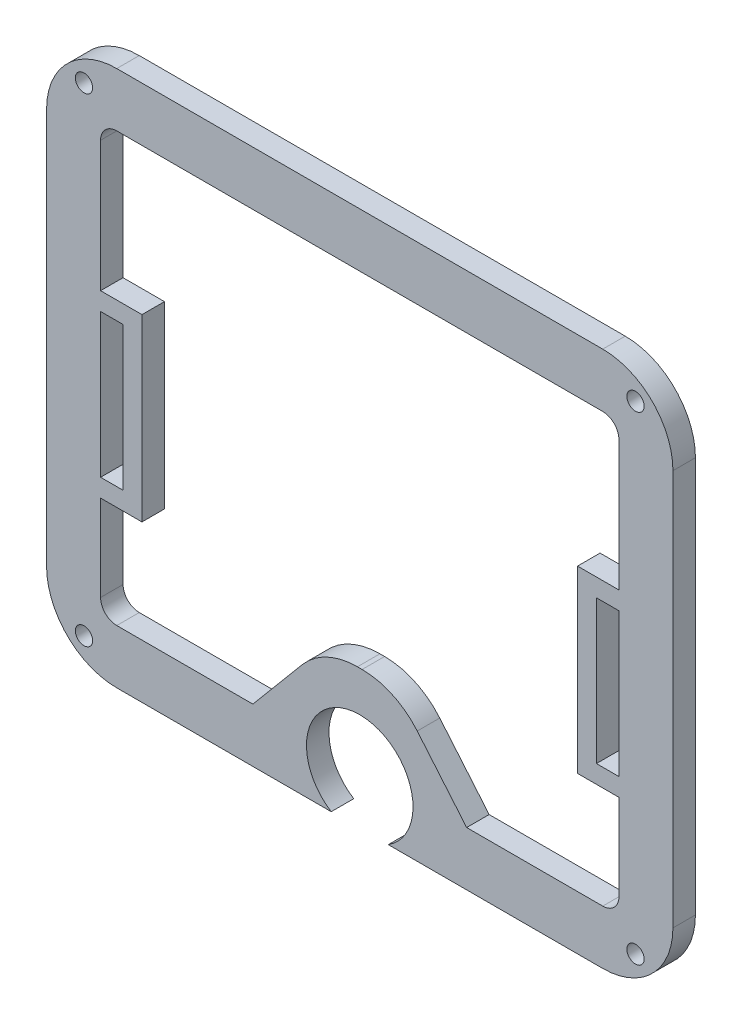
SolidWorks part; units mm, degrees
material "Delrin"
ref_plane "Front Plane" through (0, 0, 0) normal (0, 0, 1) x (1, 0, 0)
ref_plane "Top Plane" through (0, 0, 0) normal (0, 1, 0) x (1, 0, 0)
ref_plane "Right Plane" through (0, 0, 0) normal (1, 0, 0) x (0, 0, -1)
sketch "Sketch1" plane through (0, 0, 0) normal (0, 0, 1) x (1, 0, 0)
  line L0 (-17.145, -18.923) -> (-2.0127, -18.923)
  line L1 (-18.288, 13.97) -> (-18.288, -13.97)
  line L2 (-17.145, -15.113) -> (-7.5425, -15.113)
  line L3 (7.5425, -15.113) -> (17.145, -15.113)
  line L4 (18.288, 13.97) -> (18.288, -13.97)
  line L5 (-1000, 0) -> (49000, 0) construction
  line L7 (2.0127, -18.923) -> (17.145, -18.923)
  line L8 (17.145, 15.113) -> (-17.145, 15.113)
  line L9 (-7.5425, -15.113) -> (-4.0566, -10.9586)
  line L10 (-22.098, 13.97) -> (-22.098, -13.97)
  line L11 (7.5425, -15.113) -> (4.0566, -10.9586)
  line L12 (-0.1651, -9.144) -> (0.1651, -9.144)
  line L13 (22.098, 13.97) -> (22.098, -13.97)
  line L14 (17.145, 18.923) -> (-17.145, 18.923)
  line L18 (0, 12.5532) -> (0, -24.2768) construction
  arc A0 (2.0127, -18.923) -> (-2.0127, -18.923) centre (0, -15.748) ccw
  arc A1 (-17.145, -15.113) -> (-18.288, -13.97) centre (-17.145, -13.97) cw
  arc A2 (-0.1651, -9.144) -> (-4.0566, -10.9586) centre (-0.1651, -14.224) ccw
  arc A3 (18.288, -13.97) -> (17.145, -15.113) centre (17.145, -13.97) cw
  arc A4 (17.145, 15.113) -> (18.288, 13.97) centre (17.145, 13.97) cw
  arc A5 (-17.145, -18.923) -> (-22.098, -13.97) centre (-17.145, -13.97) cw
  arc A6 (22.098, -13.97) -> (17.145, -18.923) centre (17.145, -13.97) cw
  arc A7 (17.145, 18.923) -> (22.098, 13.97) centre (17.145, 13.97) cw
  arc A8 (-17.145, 18.923) -> (-22.098, 13.97) centre (-17.145, 13.97) ccw
  circle A9 centre (-19.4575, 16.891) radius 0.6096
  circle A10 centre (19.4575, 16.891) radius 0.6096
  arc A11 (-17.145, 15.113) -> (-18.288, 13.97) centre (-17.145, 13.97) ccw
  arc A12 (0.1651, -9.144) -> (4.0566, -10.9586) centre (0.1651, -14.224) cw
  circle A13 centre (19.4575, -16.891) radius 0.6096
  circle A14 centre (-19.4575, -16.891) radius 0.6096
  arc A18 (7.5425, -15.113) -> (-7.5425, -15.113) centre (0, -15.748) ccw construction
  point P0 (0, 0)
  dimension "D4" = 3.175
  dimension "D6" = 37.846
  dimension "D7" = 44.196
  dimension "D8" = 3.81
  dimension "D9" = 6.604
  dimension "D5" = 1.2192
  dimension "D2" = 4.953
  dimension "D3" = 7.5184
  dimension "D10" = 5.08
  dimension "D11" = 5.08
  dimension "D12" = 16.891
  dimension "D13" = 19.4575
extrude "Boss-Extrude1" add sketch "Sketch1" along normal blind 1.5875
sketch "Sketch2" plane through (-18.288, 0, 0) normal (1, 0, 0) x (0, 0, -1)
  line L0 (0, 3.5062) -> (-1.5875, 3.5062)
  line L1 (0, -6.625) -> (-1.5875, -6.625) construction
  line L2 (-1.5875, -15.113) -> (0, -15.113)
  line L3 (-1.5875, -15.113) -> (0, -15.113) construction
  line L4 (0, -13.97) -> (0, 13.97)
  line L5 (0, 13.97) -> (-1.5875, 13.97)
  line L6 (-1.5875, 13.97) -> (-1.5875, -13.97)
  line L7 (0, 13.97) -> (-1.5875, 13.97)
  line L8 (0, -13.97) -> (0, 4.7762)
  line L9 (-1.5875, -15.113) -> (-1.5875, -7.895)
  line L10 (-1.5875, 4.7762) -> (-1.5875, -13.97)
  line L11 (-1.5875, -13.97) -> (0, -13.97)
  line L12 (0, -15.113) -> (0, -7.895)
  line L13 (0, 4.7762) -> (-1.5875, 4.7762)
  line L14 (-1.5875, 3.5062) -> (-1.5875, -6.6447)
  line L15 (-1.5875, 4.7762) -> (-1.5875, 3.5062)
  line L16 (0, 3.5062) -> (0, 4.7762)
  line L17 (0, -7.9147) -> (0, 1.6011)
  line L18 (-1.5875, -7.9147) -> (-1.5875, -6.6447)
  line L19 (0, -6.625) -> (-1.5875, -6.625)
  line L21 (0, -7.895) -> (-1.5875, -7.895)
  line L22 (0, -7.895) -> (0, -13.97)
  line L23 (-1.5875, -7.895) -> (-1.5875, -13.97)
  line L24 (37.1441, 3.2256) -> (-46.6286, 3.8583) construction
  line L25 (-2.1172, 1.6171) -> (-43.509, 1.9297) construction
  line L28 (-1.5875, -13.97) -> (0, -13.97)
  line L29 (36.639, -9.3051) -> (-46.9129, -3.1934) construction
  line M5 (0, -13.97) -> (0, 13.97)
  line M7 (-1.5875, 13.97) -> (-1.5875, -13.97)
  dimension "D1" = 0
  dimension "D2" = 1.27
  dimension "D4" = 1.27
extrude "Boss-Extrude2" add sketch "Sketch2" along normal blind 2.921 contours L13 L10 L0 M5 | L19 L17 L8 L0 L10 M7 | L21 L8 L19 L18 M5 M7 region at (-18.288, -1.5594, 0.7937) region at (-18.288, 4.1412, 0.7937) region at (-18.288, -7.26, 0.7937)
extrude "Cut-Extrude1" cut sketch "Sketch2<3>" along normal blind 1.5875 contours L19 L8 L10 | L19 L17 L0 M5 M7 region at (-18.288, -1.5594, 0.7937)
sketch "Sketch2<3>" plane through (-18.288, 0, 0) normal (1, 0, 0) x (0, 0, -1) same geometry as "Sketch2"
mirror "Mirror1" about plane through (0, 0, 0) normal (1, 0, 0) of "Cut-Extrude1", "Boss-Extrude2"
